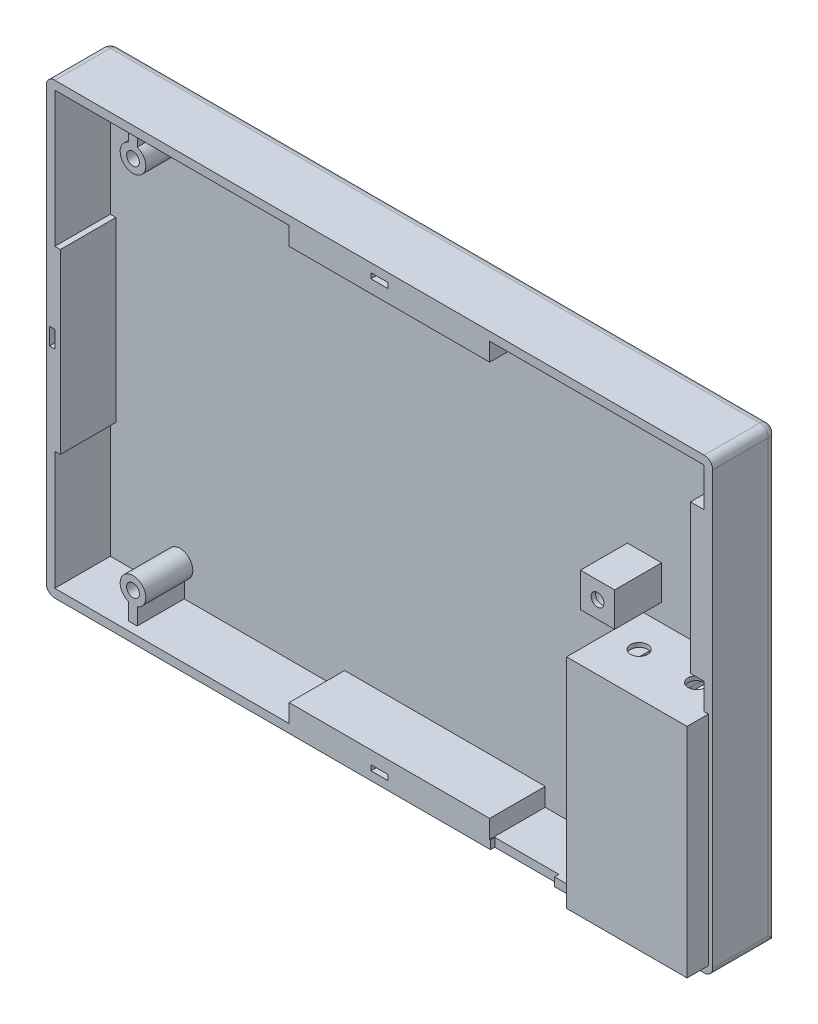
SolidWorks part; units mm, degrees
material "ABS"
ref_plane "Front Plane" through (0, 0, 0) normal (0, 0, 1) x (1, 0, 0)
ref_plane "Top Plane" through (0, 0, 0) normal (0, 1, 0) x (1, 0, 0)
ref_plane "Right Plane" through (0, 0, 0) normal (1, 0, 0) x (0, 0, -1)
sketch "Sketch2" plane through (0, 0, 0) normal (0, 0, 1) x (1, 0, 0)
  line L1 (0, 0) -> (156, 0)
  line L2 (0, 0) -> (0, 105)
  line L3 (0, 105) -> (156, 105)
  line L4 (156, 0) -> (156, 105)
  dimension "D1" = 105
  dimension "D2" = 156
extrude "Boss-Extrude1" add sketch "Sketch2" along normal blind 15
shell "Shell1" thickness 2 removed face at (78, 52.5, 15)
ref_plane "Plane1" through (0, 52.5, 0) normal (0, -1, 0) x (-1, 0, 0)
ref_plane "Plane2" through (78, 0, 0) normal (-1, 0, 0) x (0, 0, 1)
sketch "Sketch16" plane through (0, 0, 2) normal (0, 0, 1) x (1, 0, 0)
  line L0 (2, 103) -> (2, 2) construction
  line L1 (2, 71.3268) -> (3.3, 71.3268)
  line L2 (2, 71.3268) -> (2, 29.7884)
  line L3 (2, 29.7884) -> (3.3, 29.7884)
  line L4 (3.3, 71.3268) -> (3.3, 29.7884)
  dimension "D1" = 1.3
extrude "Boss-Extrude7" add sketch "Sketch16" along normal blind 13
sketch "Sketch17" plane through (0, 0, 2) normal (0, 0, 1) x (1, 0, 0)
  line L0 (154, 103) -> (2, 103) construction
  line L1 (56.8485, 103) -> (103.7984, 103)
  line L2 (56.8485, 103) -> (56.8485, 101.25)
  line L3 (56.8485, 101.25) -> (103.7984, 101.25)
  line L4 (103.7984, 103) -> (103.7984, 101.25)
  dimension "D1" = 1.75
extrude "Boss-Extrude8" add sketch "Sketch17" along normal blind 13
sketch "Sketch18" plane through (0, 0, 2) normal (0, 0, 1) x (1, 0, 0)
  line L1 (154, 2) -> (126.8, 2)
  line L2 (154, 2) -> (154, 53)
  line L3 (154, 53) -> (126.8, 53)
  line L4 (126.8, 2) -> (126.8, 53)
  dimension "D1" = 51
  dimension "D2" = 27.2
extrude "Boss-Extrude9" add sketch "Sketch18" along normal blind 18
shell "Shell2" thickness 1 removed face at (140.4, 2, 17.5) removed face at (154, 27.5, 17.5)
sketch "Sketch19" plane through (0, 0, 0) normal (0, 0, -1) x (-1, 0, 0)
  line L0 (-156, 0) -> (-156, 105) construction
  line L1 (-154, 0) -> (-127.8, 0)
  line L2 (-154, 0) -> (-154, 52)
  line L3 (-154, 52) -> (-127.8, 52)
  line L4 (-127.8, 0) -> (-127.8, 52)
  line L6 (0, 0) -> (-156, 0) construction
  dimension "D1" = 26.2
  dimension "D2" = 2
  dimension "D3" = 52
extrude "Cut-Extrude9" cut sketch "Sketch19" against normal blind 2
sketch "Sketch23" plane through (0, 0, 14) normal (0, 0, -1) x (-1, 0, 0)
sketch "Sketch24" plane through (0, 0, 14) normal (0, 0, -1) x (-1, 0, 0)
  line L1 (-154.8915, 51.9295) -> (-154, 51.9295)
  line L2 (-154.8915, 51.9295) -> (-154.8915, 1)
  line L3 (-154.8915, 1) -> (-154, 1)
  line L4 (-154, 51.9295) -> (-154, 1)
extrude "Boss-Extrude10" add sketch "Sketch24" along normal through all
sketch "Sketch25" plane through (0, 0, 14) normal (0, 0, -1) x (-1, 0, 0)
  line L1 (-127.8, 1) -> (-154, 1)
  line L2 (-127.8, 1) -> (-127.8, 2)
  line L3 (-127.8, 2) -> (-154, 2)
  line L4 (-154, 1) -> (-154, 2)
extrude "Boss-Extrude11" add sketch "Sketch25" along normal blind 12
sketch "Sketch27" plane through (0, 0, 19) normal (0, 0, -1) x (-1, 0, 0)
  line L0 (-154, 52) -> (-154, 0) construction
  line L1 (-154, 48.5) -> (-127.8, 48.5)
  line L2 (-154, 48.5) -> (-154, 47.5)
  line L3 (-154, 47.5) -> (-127.8, 47.5)
  line L4 (-127.8, 48.5) -> (-127.8, 47.5)
  line L5 (-127.8, 0) -> (-127.8, 52) construction
  line L6 (-154, 52) -> (-127.8, 52) construction
  dimension "D1" = 3.5
  dimension "1" = 1
extrude "Boss-Extrude12" add sketch "Sketch27" along normal blind 18
sketch "Sketch28" plane through (0, 0, 1) normal (0, 0, -1) x (-1, 0, 0)
  line L0 (-127.8, 48.5) -> (-154, 48.5) construction
  line L1 (-152, 48.5) -> (-143, 48.5)
  line L2 (-152, 48.5) -> (-152, 47.5)
  line L3 (-152, 47.5) -> (-143, 47.5)
  line L4 (-143, 48.5) -> (-143, 47.5)
  line L5 (-154, 47.5) -> (-127.8, 47.5) construction
  line L6 (-154, 52) -> (-154, 0) construction
  point P10 (-154, 26)
  point P11 (-143, 48)
  dimension "D1" = 2
  dimension "D2" = 11
extrude "Cut-Extrude10" cut sketch "Sketch28" against normal blind 14
sketch "Sketch29" plane through (0, 0, 1) normal (0, 0, -1) x (-1, 0, 0)
  line L0 (-127.8, 48.5) -> (-143, 48.5) construction
  line L1 (-137.8, 48.5) -> (-130.8, 48.5)
  line L2 (-137.8, 48.5) -> (-137.8, 47.5)
  line L3 (-137.8, 47.5) -> (-130.8, 47.5)
  line L4 (-130.8, 48.5) -> (-130.8, 47.5)
  line L5 (-154, 47.5) -> (-127.8, 47.5) construction
  line L6 (-127.8, 0) -> (-127.8, 52) construction
  line L7 (-127.8, 47.5) -> (-127.8, 48.5) construction
  dimension "D1" = 3
  dimension "D2" = 10
extrude "Cut-Extrude11" cut sketch "Sketch29" against normal blind 13
sketch "Sketch30" plane through (0, 0, 0) normal (0, 0, -1) x (-1, 0, 0)
  line L1 (-127.8, 0) -> (-127.3, 0)
  line L2 (-127.8, 0) -> (-127.8, 52)
  line L3 (-127.8, 52) -> (-127.3, 52)
  line L4 (-127.3, 0) -> (-127.3, 52)
  dimension "D1" = 0.5
extrude "Cut-Extrude12" cut sketch "Sketch30" against normal blind 1
sketch "Sketch31" plane through (0, 0, 0) normal (0, 0, -1) x (-1, 0, 0)
  line L0 (-127.3, 52) -> (-154, 52) construction
  line L1 (-154, 0) -> (-154.5, 0)
  line L2 (-154, 0) -> (-154, 52)
  line L3 (-154, 52) -> (-154.5, 52)
  line L4 (-154.5, 0) -> (-154.5, 52)
  dimension "D1" = 0.5
extrude "Cut-Extrude13" cut sketch "Sketch31" against normal blind 1
sketch "Sketch32" plane through (0, 0, 1) normal (0, 0, -1) x (-1, 0, 0)
  line L0 (-137.8, 48.5) -> (-137.8, 47.5) construction
  line L1 (-143, 47.5) -> (-137.8, 47.5)
  line L2 (-143, 47.5) -> (-143, 48.5)
  line L3 (-143, 48.5) -> (-137.8, 48.5)
  line L4 (-137.8, 47.5) -> (-137.8, 48.5)
  line L5 (-137.8, 48.5) -> (-143, 48.5) construction
extrude "Boss-Extrude13" add sketch "Sketch32" along normal blind 1
sketch "Sketch34" plane through (0, 0, 0) normal (0, 0, -1) x (-1, 0, 0)
  line L1 (-137.8, 48.5) -> (-143, 48.5)
  line L2 (-137.8, 48.5) -> (-137.8, 47.5)
  line L3 (-137.8, 47.5) -> (-143, 47.5)
  line L4 (-143, 48.5) -> (-143, 47.5)
extrude "Boss-Extrude14" add sketch "Sketch34" along normal blind 1
sketch "Sketch35" plane through (0, 0, 19) normal (0, 0, -1) x (-1, 0, 0)
  line L0 (-127.3, 52) -> (-154.5, 52) construction
  line L1 (-137.8, 48.5) -> (-142.9906, 48.5)
  line L2 (-137.8, 48.5) -> (-137.8, 52)
  line L3 (-137.8, 52) -> (-142.9906, 52)
  line L4 (-142.9906, 48.5) -> (-142.9906, 52)
extrude "Boss-Extrude15" add sketch "Sketch35" along normal blind 20
sketch "Sketch38" plane through (0, 0, 14) normal (0, 0, -1) x (-1, 0, 0)
  line L1 (-154.5, 51.9295) -> (-154, 51.9295)
  line L2 (-154.5, 51.9295) -> (-154.5, 52)
  line L3 (-154.5, 52) -> (-154, 52)
  line L4 (-154, 51.9295) -> (-154, 52)
extrude "Cut-Extrude14" cut sketch "Sketch38" against normal blind 1
sketch "Sketch41" plane through (0, 52, 0) normal (0, -1, 0) x (1, 0, 0)
  line L0 (126.8, 20) -> (154, 20) construction
  circle A0 centre (147.2493, 10) radius 2
  dimension "D1" = 10
extrude "Cut-Extrude15" cut sketch "Sketch41" against normal blind 1
sketch "Sketch42" plane through (0, 52, 0) normal (0, -1, 0) x (1, 0, 0)
  line L0 (126.8, 20) -> (154, 20) construction
  circle A0 centre (133.7932, 10) radius 2
  dimension "D1" = 10
  dimension "D2" = 4
extrude "Cut-Extrude16" cut sketch "Sketch42" against normal blind 1
sketch "Sketch43" plane through (0, 0, -1) normal (0, 0, -1) x (-1, 0, 0)
  line L1 (-142.9906, 52) -> (-137.8, 52)
  line L2 (-142.9906, 52) -> (-142.9906, 47.5)
  line L3 (-142.9906, 47.5) -> (-137.8, 47.5)
  line L4 (-137.8, 52) -> (-137.8, 47.5)
extrude "Cut-Extrude17" cut sketch "Sketch43" against normal blind 1
sketch "Sketch44" plane through (0, 0, 15) normal (0, 0, 1) x (1, 0, 0)
  line L1 (154, 53) -> (155, 53)
  line L2 (154, 53) -> (154, 1.9939)
  line L3 (154, 1.9939) -> (155, 1.9939)
  line L4 (155, 53) -> (155, 1.9939)
  dimension "D1" = 1
extrude "Boss-Extrude16" add sketch "Sketch44" along normal blind 5
sketch "Sketch46" plane through (0, 47.5, 0) normal (0, -1, 0) x (1, 0, 0)
  line L0 (142.9906, 0) -> (137.8, 0) construction
  line L1 (138.3, 2) -> (142.5, 2)
  line L2 (138.3, 2) -> (138.3, 1)
  line L3 (138.3, 1) -> (142.5, 1)
  line L4 (142.5, 2) -> (142.5, 1)
  line L5 (143, 15) -> (143, -1) construction
  line L6 (137.8, 14) -> (137.8, 0) construction
  dimension "D1" = 1
  dimension "D2" = 1
  dimension "D3" = 0.5
  dimension "D4" = 0.5
extrude "Cut-Extrude18" cut sketch "Sketch46" against normal blind 4.5
sketch "Sketch47" plane through (0, 0, 2) normal (0, 0, -1) x (-1, 0, 0)
  line L0 (-127.8, 2) -> (-154, 2) construction
  line L1 (-154.5, 2) -> (-127.3, 2)
  line L2 (-154.5, 2) -> (-154.5, 0)
  line L3 (-154.5, 0) -> (-127.3, 0)
  line L4 (-127.3, 2) -> (-127.3, 0)
  line L5 (-154, 0) -> (-127.8, 0) construction
  line L6 (-154.5, 51.9295) -> (-154.5, 0) construction
  line L7 (-127.3, 0) -> (-127.3, 52) construction
  dimension "D1" = 0
  dimension "D2" = 0
extrude "Cut-Extrude19" cut sketch "Sketch47" against normal blind 2 and the other way blind 2
mirror "Mirror3" about plane through (0, 52.5, 0) normal (0, -1, 0) of "Boss-Extrude8"
sketch "Sketch50" plane through (0, 0, 2) normal (0, 0, 1) x (1, 0, 0)
  line L0 (154, 53) -> (154, 103) construction
  line L1 (154, 93.9217) -> (150.8, 93.9217)
  line L2 (154, 93.9217) -> (154, 59.1499)
  line L3 (154, 59.1499) -> (150.8, 59.1499)
  line L4 (150.8, 93.9217) -> (150.8, 59.1499)
  dimension "D1" = 3.2
extrude "Boss-Extrude17" add sketch "Sketch50" along normal blind 13
sketch "Sketch51" plane through (0, 0, 0) normal (0, 0, 1) x (1, 0, 0)
  line L0 (3.3, 29.7884) -> (3.3, 71.3268) construction
  line L1 (56.8485, 101.25) -> (103.7984, 101.25) construction
  circle A0 centre (18.3, 96.25) radius 3
  dimension "D1" = 6
  dimension "D2" = 15
  dimension "D3" = 5
extrude "Boss-Extrude18" add sketch "Sketch51" along normal blind 13
sketch "Sketch54" plane through (0, 0, 13) normal (0, 0, 1) x (1, 0, 0)
  circle A0 centre (18.3, 96.25) radius 1.5
extrude "Cut-Extrude20" cut sketch "Sketch54" against normal blind 6
mirror "Mirror4" about plane through (0, 52.5, 0) normal (0, -1, 0) of "Cut-Extrude20", "Boss-Extrude18"
sketch "Sketch56" plane through (0, 0, 15) normal (0, 0, 1) x (1, 0, 0)
  line L0 (56.8485, 103) -> (2, 103) construction
  line L1 (76, 103) -> (80, 103)
  line L2 (76, 103) -> (76, 101.75)
  line L3 (76, 101.75) -> (80, 101.75)
  line L4 (80, 103) -> (80, 101.75)
  line L5 (78, 8.25) -> (78, -8.25) construction
  dimension "D1" = 1.25
  dimension "D2" = 0
  dimension "D3" = 2
  dimension "D4" = 2
extrude "Cut-Extrude21" cut sketch "Sketch56" against normal blind 3
mirror "Mirror5" about plane through (0, 52.5, 0) normal (0, -1, 0) of "Cut-Extrude21"
sketch "Sketch57" plane through (0, 0, 15) normal (0, 0, 1) x (1, 0, 0)
  line L0 (2, 103) -> (2, 71.3268) construction
  line L1 (2, 54.5) -> (0.75, 54.5)
  line L2 (2, 54.5) -> (2, 50.5)
  line L3 (2, 50.5) -> (0.75, 50.5)
  line L4 (0.75, 54.5) -> (0.75, 50.5)
  line L5 (-8.25, 52.5) -> (8.25, 52.5) construction
  dimension "D1" = 1.25
  dimension "D2" = 0
  dimension "D3" = 2
  dimension "D4" = 2
extrude "Cut-Extrude22" cut sketch "Sketch57" against normal blind 3
sketch "Sketch60" plane through (0, 0, 0) normal (0, -1, 0) x (1, 0, 0)
  line L0 (0, 15) -> (156, 15) construction
  line L1 (119, 15) -> (104, 15)
  line L2 (119, 15) -> (119, 14)
  line L3 (119, 14) -> (104, 14)
  line L4 (104, 15) -> (104, 14)
  line L5 (156, 15) -> (156, 0) construction
  dimension "D1" = 1
  dimension "D2" = 15
  dimension "D3" = 37
extrude "Cut-Extrude24" cut sketch "Sketch60" against normal blind 2
sketch "Sketch62" plane through (0, 0, 0) normal (0, 0, -1) x (-1, 0, 0)
  line L0 (-156, 0) -> (-156, 105) construction
  line L1 (-131.05, 65.2) -> (-123.05, 65.2)
  line L2 (-131.05, 65.2) -> (-131.05, 57.2)
  line L3 (-131.05, 57.2) -> (-123.05, 57.2)
  line L4 (-123.05, 65.2) -> (-123.05, 57.2)
  line L5 (-156, 105) -> (0, 105) construction
  dimension "D1" = 8
  dimension "D2" = 8
  dimension "D3" = 24.95
  dimension "D4" = 39.8
extrude "Boss-Extrude19" add sketch "Sketch62" against normal blind 13
sketch "Sketch63" plane through (0, 0, 13) normal (0, 0, 1) x (1, 0, 0)
  line L0 (131.05, 65.2) -> (131.05, 57.2) construction
  line L1 (123.05, 65.2) -> (131.05, 65.2) construction
  circle A0 centre (127.05, 61.2) radius 1.5
  dimension "D1" = 4
  dimension "D3" = 3
  dimension "D2" = 4
sketch "Sketch64" plane through (0, 0, 0) normal (0, 0, -1) x (-1, 0, 0)
  line L0 (-156, 0) -> (-156, 105) construction
  line L1 (-156, 105) -> (0, 105) construction
  circle A0 centre (-127.05, 61.2) radius 3
  dimension "D1" = 43.8
  dimension "28.95" = 28.95
extrude "Cut-Extrude25" cut sketch "Sketch64" against normal blind 12
extrude "Cut-Extrude26" cut sketch "Sketch63" against normal blind 1
fillet "Fillet1" radius 2 8 edges at (0, 0, 7.5) (156, 0, 7.5) (0, 105, 7.5) (0, 52.5, 0) (63.65, 0, 0) (156, 52.5, 0) (156, 105, 7.5) (78, 105, 0)
sketch "Sketch66" plane through (0, 0, 2) normal (0, 0, 1) x (1, 0, 0)
  line L0 (103.7984, 101.25) -> (103.7984, 103) construction
  line L1 (56.8485, 101.25) -> (103.7984, 101.25)
  line L2 (56.8485, 101.25) -> (56.8485, 98.75)
  line L3 (56.8485, 98.75) -> (103.7984, 98.75)
  line L4 (103.7984, 101.25) -> (103.7984, 98.75)
  point P7 (103.7984, 102.125)
  dimension "D1" = 2.5
  dimension "D2" = 0
extrude "Boss-Extrude20" add sketch "Sketch66" along normal blind 13
mirror "Mirror6" about plane through (0, 52.5, 0) normal (0, -1, 0) of "Boss-Extrude20"
sketch "Sketch69" plane through (0, 0, 13) normal (0, 0, 1) x (1, 0, 0)
  line L0 (18.3, 99.25) -> (18.3, 103)
  line L1 (56.8485, 103) -> (2, 103) construction
  circle A0 centre (18.3, 96.25) radius 3 construction
  circle A1 centre (18.3, 96.25) radius 3 construction
rib "Rib1" sketch "Sketch69" sketch "Sketch69" thickness 2 extrusion direction normal to sketch draft on no parameters "D1"=2
sketch "Sketch70" plane through (0, 0, 13) normal (0, 0, 1) x (1, 0, 0)
  line L0 (18.3, 5.75) -> (18.3, 2)
  line L1 (2, 2) -> (56.8485, 2) construction
  circle A0 centre (18.3, 8.75) radius 3 construction
rib "Rib2" sketch "Sketch70" sketch "Sketch70" thickness 2 extrusion direction normal to sketch draft on no parameters "D1"=2
